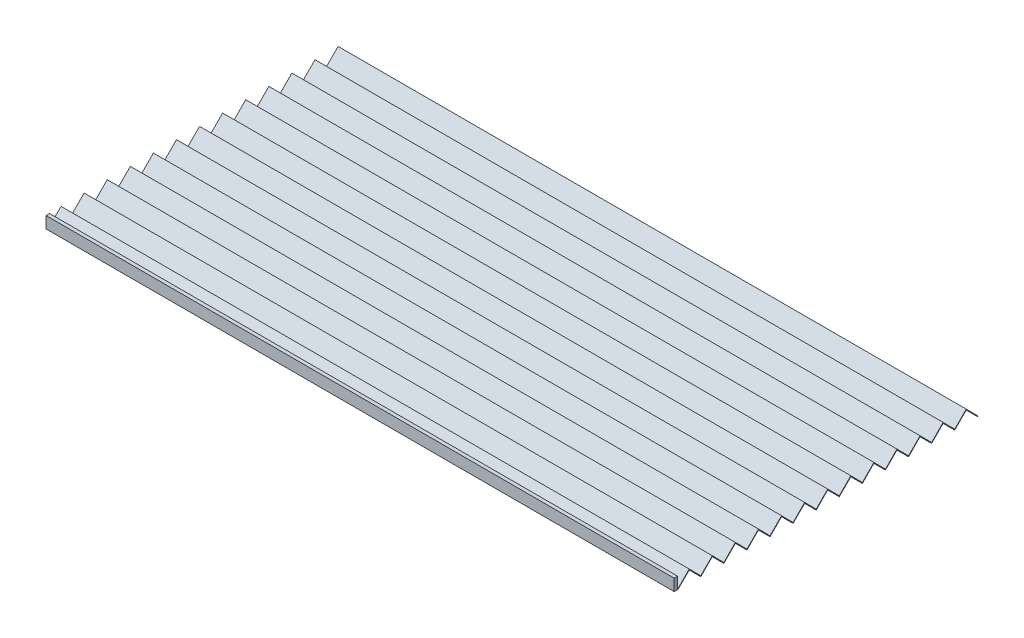
SolidWorks part; units mm, degrees
ref_plane "Front Plane" through (0, 0, 0) normal (0, 0, 1) x (1, 0, 0)
ref_plane "Top Plane" through (0, 0, 0) normal (0, 1, 0) x (1, 0, 0)
ref_plane "Right Plane" through (0, 0, 0) normal (1, 0, 0) x (0, 0, -1)
sketch "Sketch2" plane through (0, 0, 0) normal (0, 0, 1) x (1, 0, 0)
  line L1 (-270, 10) -> (270, 10)
  line L2 (-270, 10) -> (-270, 0)
  line L3 (-270, 0) -> (270, 0)
  line L4 (270, 10) -> (270, 0)
  point P4 (0, 0)
  dimension "D1" = 10
  dimension "D2" = 540
extrude "Boss-Extrude1" add sketch "Sketch2" along normal blind 3
sketch "Sketch3" plane through (270, 0, 0) normal (1, 0, 0) x (0, 0, -1)
  line L0 (0, 10) -> (257.976, 10) construction
  line L1 (0, 0) -> (257.976, 0) construction
  line L3 (0, 0) -> (9.9222, 10)
  line L4 (9.9222, 10) -> (19.8443, 0)
  line L5 (19.8443, 0) -> (29.7665, 10)
  line L6 (29.7665, 10) -> (39.6886, 0)
  line L7 (39.6886, 0) -> (49.6108, 10)
  line L8 (49.6108, 10) -> (59.5329, 0)
  line L9 (59.5329, 0) -> (69.4551, 10)
  line L10 (69.4551, 10) -> (79.3772, 0)
  line L11 (79.3772, 0) -> (89.2994, 10)
  line L12 (89.2994, 10) -> (99.2215, 0)
  line L13 (99.2215, 0) -> (109.1437, 10)
  line L14 (109.1437, 10) -> (119.0658, 0)
  line L15 (119.0658, 0) -> (128.988, 10)
  line L16 (128.988, 10) -> (138.9101, 0)
  line L17 (138.9101, 0) -> (148.8323, 10)
  line L18 (148.8323, 10) -> (158.7544, 0)
  line L20 (158.7544, 0) -> (168.6766, 10)
  line L21 (168.6766, 10) -> (178.5987, 0)
  line L22 (178.5987, 0) -> (188.5209, 10)
  line L23 (188.5209, 10) -> (198.4431, 0)
  line L24 (198.4431, 0) -> (208.3652, 10)
  line L25 (208.3652, 10) -> (218.2874, 0)
  line L26 (218.2874, 0) -> (228.2095, 10)
  line L27 (228.2095, 10) -> (238.1317, 0)
  line L28 (238.1317, 0) -> (248.0538, 10)
  line L29 (248.0538, 10) -> (257.976, 0)
  line L30 (257.976, 10) -> (257.976, 0) construction
  line L32 (257.976, 10) -> (257.976, 0) construction
extrude "Extrude-Thin1" add sketch "Sketch3" against normal through all thin thin type mid plane wall 0.5
